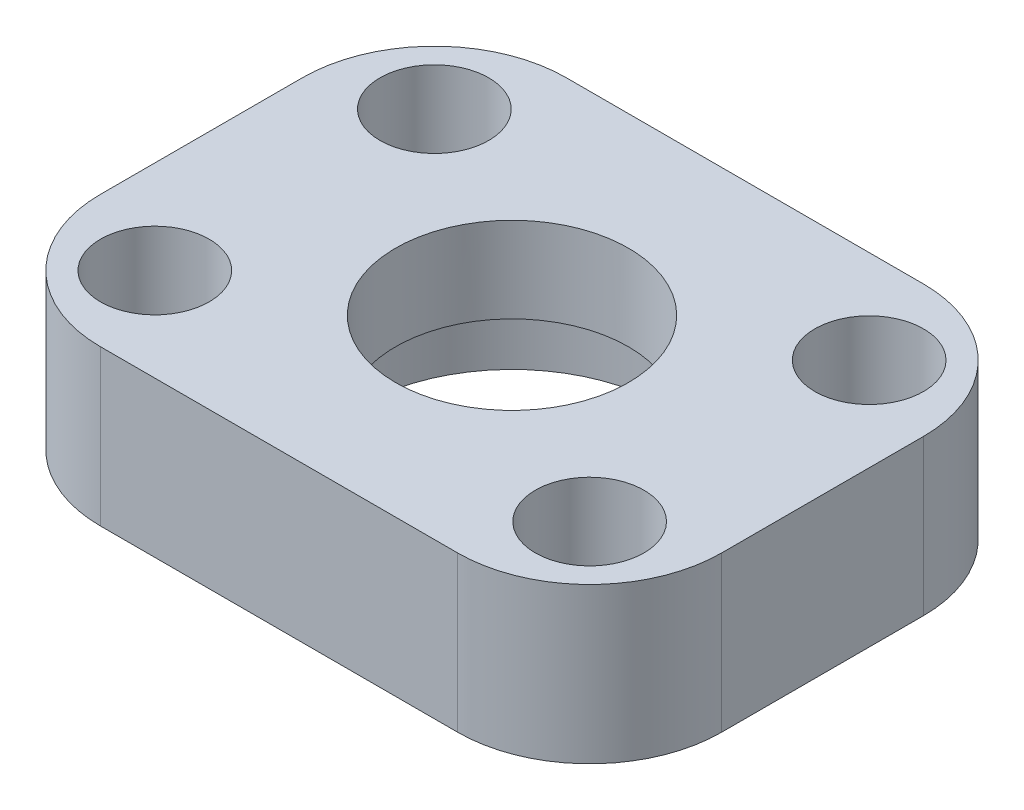
SolidWorks part; units mm, degrees
ref_plane "Front Plane" through (0, 0, 0) normal (0, 0, 1) x (1, 0, 0)
ref_plane "Top Plane" through (0, 0, 0) normal (0, 1, 0) x (1, 0, 0)
ref_plane "Right Plane" through (0, 0, 0) normal (1, 0, 0) x (0, 0, -1)
sketch "Sketch1" plane through (0, 0, 0) normal (0, 1, 0) x (1, 0, 0)
  line L1 (-20, 15) -> (20, 15)
  line L2 (-20, 15) -> (-20, -15)
  line L3 (-20, -15) -> (20, -15)
  line L4 (20, 15) -> (20, -15)
  line L5 (-20, 15) -> (20, -15) construction
  line L6 (-20, -15) -> (20, 15) construction
  point P0 (0, 0)
  dimension "D1" = 30
  dimension "D2" = 40
extrude "Boss-Extrude1" add sketch "Sketch1" along normal blind 10
sketch "Sketch3" plane through (0, 0, 0) normal (0, -1, 0) x (1, 0, 0)
  circle A0 centre (0, 0) radius 9.875
  dimension "D1" = 19.75
extrude "Cut-Extrude1" cut sketch "Sketch3" against normal blind 4.5
sketch "Sketch4" plane through (0, 10, 0) normal (0, 1, 0) x (1, 0, 0)
  circle A0 centre (0, 0) radius 7.5
  dimension "D1" = 15
extrude "Cut-Extrude2" cut sketch "Sketch4" against normal through all
hole_wizard "Ø3.0mm Dowel Hole1" positions "Sketch7" profile "Sketch8" hole size "Ø3.0" standard "ANSI Metric" end condition up to next
sketch "Sketch7" plane through (0, 10, 0) normal (0, 1, 0) x (1, 0, 0)
  line L0 (20, 0) -> (-20, 0) construction
  line L1 (20, -15) -> (20, 15) construction
  line L2 (-20, 15) -> (-20, -15) construction
  line L4 (0, 15) -> (0, -15) construction
  line L5 (20, 15) -> (-20, 15) construction
  line L6 (-20, -15) -> (20, -15) construction
  point P0 (-14, 9)
  point P21 (-14, -9)
  point P22 (14, -9)
  point P23 (14, 9)
  dimension "D1" = 6
  dimension "D2" = 6
sketch "Sketch8" plane through (-14, 10, -9) normal (1, 0, 0) x (0, 0, 1)
  line L0 (0, 0) -> (0, 10)
  line L1 (0, 10) -> (1.5, 10)
  line L2 (1.5, 10) -> (1.5, 0)
  line L5 (1.5, 0) -> (0, 0)
  line L11 (0, -6.35) -> (0, 107.95) construction
  dimension "Thru Hole Dia." = 3
  dimension "Thru Hole Depth" = 10
fillet "Fillet1" radius 8.5 4 edges at (20, 5, -15) (20, 5, 15) (-20, 5, 15) (-20, 5, -15)
sketch "Sketch9" plane through (0, 10, 0) normal (0, 1, 0) x (1, 0, 0)
  line L0 (14, -9) -> (-14, -9) construction
  circle A0 centre (14, -9) radius 3.5
  circle A1 centre (-14, -9) radius 3.5
  circle A2 centre (-14, 9) radius 3.5
  circle A3 centre (14, 9) radius 3.5
  point P4 (0, 0)
  dimension "D1" = 7
  dimension "D4" = 28
  dimension "D5" = 18
  dimension "D2" = 2
  dimension "D3" = 2
extrude "Cut-Extrude3" cut sketch "Sketch9" against normal blind 5
